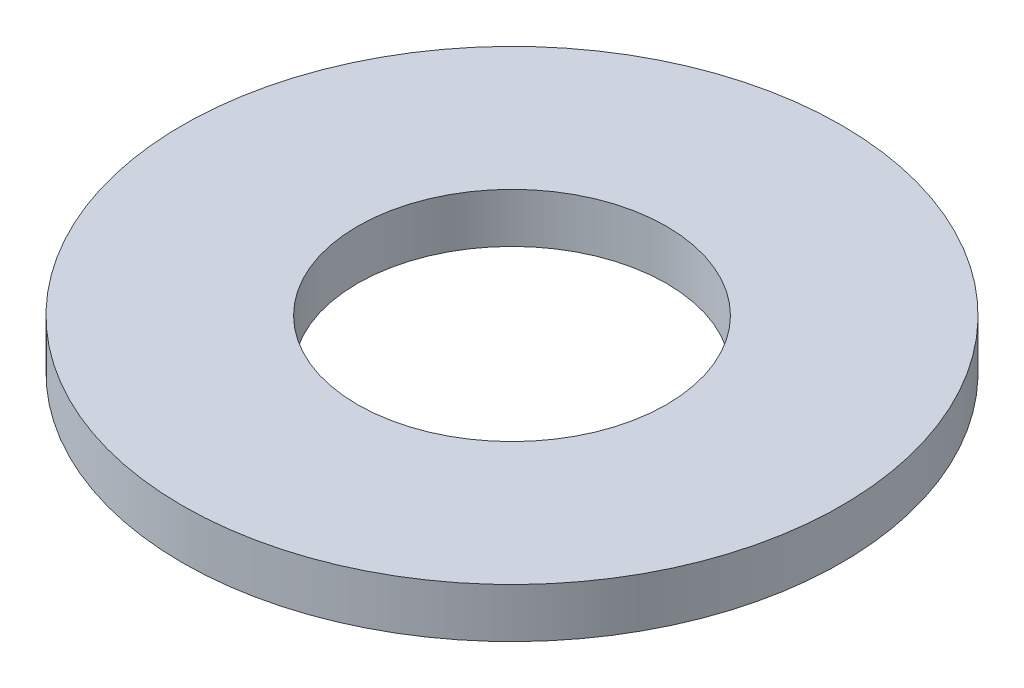
SolidWorks part; units mm, degrees
ref_plane "Front Plane" through (0, 0, 0) normal (0, 0, 1) x (1, 0, 0)
ref_plane "Top Plane" through (0, 0, 0) normal (0, 1, 0) x (1, 0, 0)
ref_plane "Right Plane" through (0, 0, 0) normal (1, 0, 0) x (0, 0, -1)
sketch "Sketch1" plane through (0, 0, 0) normal (0, 1, 0) x (1, 0, 0)
  circle A0 centre (0, 0) radius 80
  dimension "FLANGE_OD" = 160
extrude "Boss-Extrude1" add sketch "Sketch1" along normal blind 12
sketch "Sketch2" plane through (0, 0, 0) normal (0, 1, 0) x (1, 0, 0)
  circle A0 centre (0, 0) radius 37.5
  dimension "BORE_D" = 75
extrude "Cut-Extrude1" cut sketch "Sketch2" along normal through all
sketch "Sketch3" plane through (0, 12, 0) normal (0, 1, 0) x (1, 0, 0)
  circle A0 centre (0, 0) radius 23.4387 construction
  circle A1 centre (-23.4387, 0) radius 4.1837
  dimension "BOLT_D" = 8.3674
  dimension "BOLT_PCD" = 46.8773
extrude "Cut-Extrude2" cut sketch "Sketch3" against normal blind 10.4532 rebuild error yes
pattern_circular "CirPattern1" count 3 over 360 rebuild error yes
